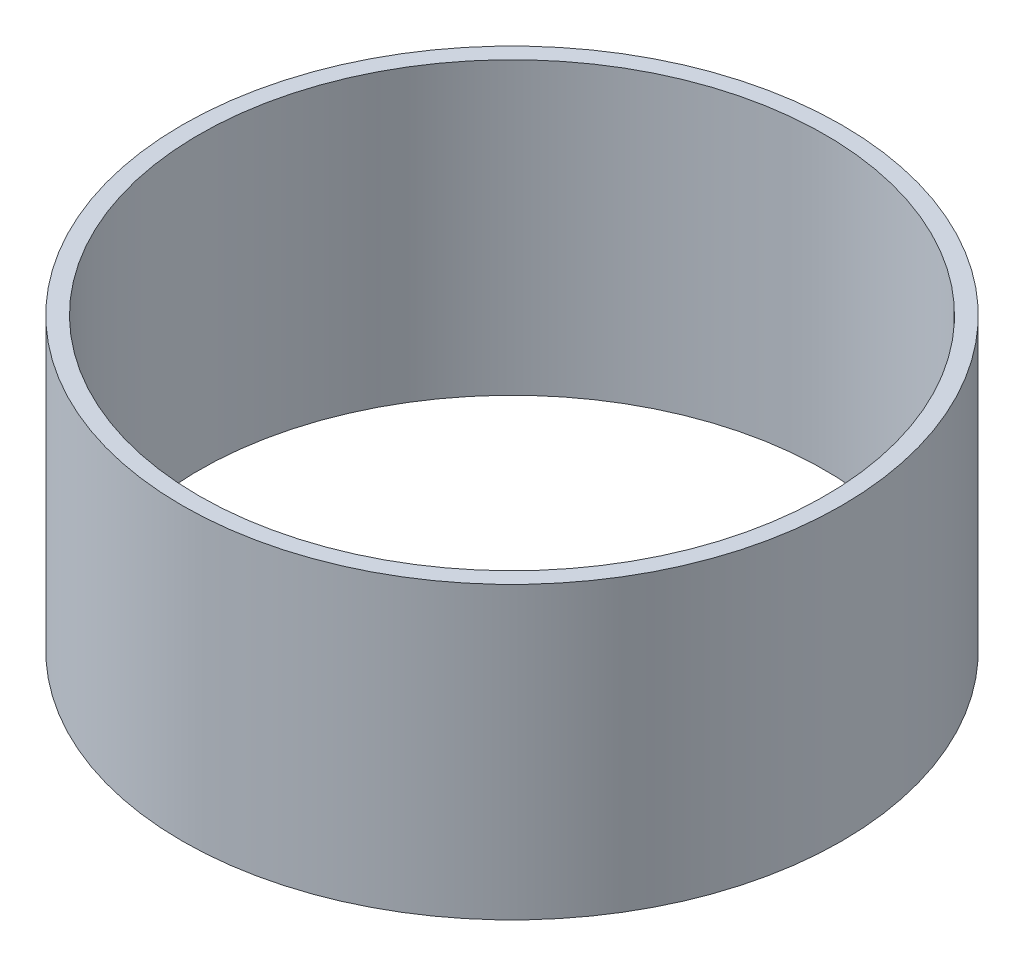
SolidWorks part; units mm, degrees
material "PVC Rigid"
ref_plane "Front Plane" through (0, 0, 0) normal (0, 0, 1) x (1, 0, 0)
ref_plane "Top Plane" through (0, 0, 0) normal (0, 1, 0) x (1, 0, 0)
ref_plane "Right Plane" through (0, 0, 0) normal (1, 0, 0) x (0, 0, -1)
sketch "Sketch1" plane through (0, 0, 0) normal (0, 1, 0) x (1, 0, 0)
  circle A0 centre (0, 0) radius 93.6625
  circle A1 centre (0, 0) radius 88.9
  dimension "D1" = 187.325
  dimension "D2" = 177.8
extrude "Boss-Extrude1" add sketch "Sketch1" along normal mid plane 82.55
ref_plane "Plane1" through (0, 0, 93.6625) normal (0, 0, 1) x (1, 0, 0)
sketch "Sketch2" plane through (0, 0, 93.6625) normal (0, 0, 1) x (1, 0, 0)
  line L0 (0, -45.4025) -> (0, 45.4025) construction
  line L1 (-93.6625, -41.275) -> (93.6625, -41.275) construction
  circle A0 centre (0, -34.925) radius 1.4351
  dimension "D1" = 2.8702
  dimension "D2" = 6.35
extrude "Cut-Extrude1" [suppressed] cut sketch "Sketch2" against normal blind 25.146
pattern_circular "CirPattern1" [suppressed] count 12 over 360 reverse direction yes of bodies 102
sketch "Sketch3" plane through (0, 0, 93.6625) normal (0, 0, 1) x (1, 0, 0)
  line L0 (0, -45.4025) -> (0, 45.4025) construction
  line L1 (88.9, 41.275) -> (-88.9, 41.275) construction
  circle A1 centre (0, 34.925) radius 1.4351
  dimension "D1" = 2.8702
  dimension "D3" = 6.35
extrude "Cut-Extrude2" [suppressed] cut sketch "Sketch3" against normal blind 25.908
pattern_circular "CirPattern2" [suppressed] count 3 over 360 of bodies 104
